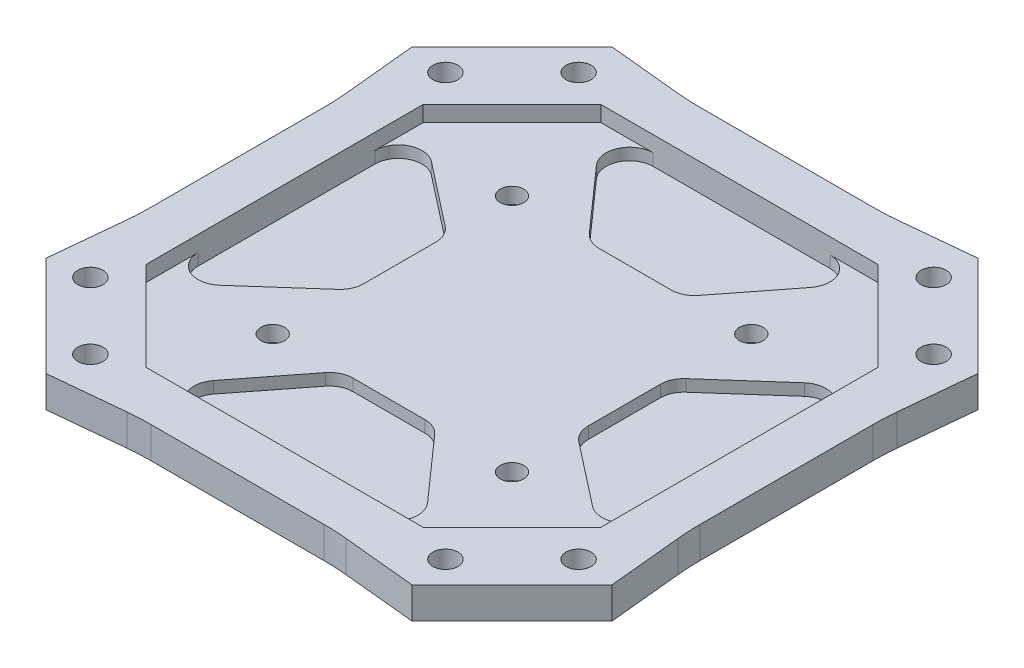
SolidWorks part; units mm, degrees
ref_plane "Front Plane" through (0, 0, 0) normal (0, 0, 1) x (1, 0, 0)
ref_plane "Top Plane" through (0, 0, 0) normal (0, 1, 0) x (1, 0, 0)
ref_plane "Right Plane" through (0, 0, 0) normal (1, 0, 0) x (0, 0, -1)
sketch "Sketch1" plane through (0, 0, 0) normal (0, 1, 0) x (1, 0, 0)
  line L0 (-35, 12.5) -> (-36.0623, 23.3344)
  line L1 (-35, 35) -> (35, 35) construction
  line L2 (-35, 35) -> (-35, -35) construction
  line L3 (-35, -35) -> (35, -35) construction
  line L4 (35, 35) -> (35, -35) construction
  line L5 (-35, 35) -> (35, -35) construction
  line L6 (-35, -35) -> (35, 35) construction
  line L7 (-23.3344, 36.0623) -> (-36.0623, 23.3344)
  line L8 (-23.3344, 36.0623) -> (-12.5, 35)
  line L9 (36.0623, 23.3344) -> (35, 12.5)
  line L10 (12.5, 35) -> (23.3344, 36.0623)
  line L11 (36.0623, 23.3344) -> (23.3344, 36.0623)
  line L12 (23.3344, -36.0623) -> (12.5, -35)
  line L13 (35, -12.5) -> (36.0623, -23.3344)
  line L14 (23.3344, -36.0623) -> (36.0623, -23.3344)
  line L15 (-36.0623, -23.3344) -> (-35, -12.5)
  line L16 (-12.5, -35) -> (-23.3344, -36.0623)
  line L17 (-36.0623, -23.3344) -> (-23.3344, -36.0623)
  line L18 (-35, 12.5) -> (-35, -12.5)
  line L19 (-12.5, 35) -> (12.5, 35)
  line L20 (35, 12.5) -> (35, -12.5)
  line L21 (12.5, -35) -> (-12.5, -35)
  line L22 (33.2339, 20.506) -> (20.506, 33.2339) construction
  line L23 (-20.506, 33.2339) -> (-33.2339, 20.506) construction
  line L24 (-33.2339, -20.506) -> (-20.506, -33.2339) construction
  line L25 (20.506, -33.2339) -> (33.2339, -20.506) construction
  circle A0 centre (31.1126, 22.6273) radius 1.6
  circle A1 centre (22.6273, 31.1126) radius 1.6
  circle A2 centre (31.1126, -22.6273) radius 1.6
  circle A3 centre (22.6273, -31.1126) radius 1.6
  circle A4 centre (-22.6273, -31.1126) radius 1.6
  circle A5 centre (-31.1126, -22.6273) radius 1.6
  circle A6 centre (-31.1126, 22.6273) radius 1.6
  circle A7 centre (-22.6273, 31.1126) radius 1.6
  point P0 (0, 0)
  point P25 (0, 0)
  point P51 (0, 0)
  dimension "D9" = 3.2
  dimension "D10" = 3.2
  dimension "D15" = 3.2
  dimension "D1" = 70
  dimension "D2" = 5.6
  dimension "D3" = 5.6
  dimension "D4" = 22.5
  dimension "D5" = 22.5
  dimension "D6" = 18
  dimension "D7" = 4
  dimension "D11" = 6
  dimension "D12" = 6
  dimension "D14" = 6
  dimension "D8" = 4
  dimension "D13" = 4
extrude "Boss-Extrude1" add sketch "Sketch1" along normal blind 4
sketch "Sketch3" plane through (0, 4, 0) normal (0, 1, 0) x (1, 0, 0)
  line L0 (35, -12.5) -> (35, 12.5) construction
  line L1 (-17.6688, 29) -> (17.6688, 29)
  line L2 (-29, 17.6688) -> (-29, -17.6688)
  line L3 (-17.6688, -29) -> (17.6688, -29)
  line L4 (29, 17.6688) -> (29, -17.6688)
  line L5 (-23.3344, 23.3344) -> (23.3344, -23.3344) construction
  line L6 (-23.3344, -23.3344) -> (23.3344, 23.3344) construction
  line L7 (12.5, 35) -> (-12.5, 35) construction
  line L8 (-35, 12.5) -> (-35, -12.5) construction
  line L9 (-12.5, -35) -> (12.5, -35) construction
  line L43 (-16.9704, 29.6984) -> (-29.6984, 16.9704)
  line L44 (-17.6688, 29) -> (-29, 17.6688)
  line L46 (-29.6984, -16.9704) -> (-16.9704, -29.6984)
  line L47 (-29, -17.6688) -> (-17.6688, -29)
  line L49 (16.9704, -29.6984) -> (29.6984, -16.9704)
  line L50 (17.6688, -29) -> (29, -17.6688)
  line L52 (29.6984, 16.9704) -> (16.9704, 29.6984)
  line L53 (29, 17.6688) -> (17.6688, 29)
  point P0 (0, 0)
  dimension "D1" = 6
  dimension "D2" = 6
  dimension "D7" = 6
  dimension "D8" = 6
  dimension "D3" = 9
  dimension "D4" = 9
  dimension "D5" = 9
  dimension "D6" = 9
extrude "Cut-Extrude1" cut sketch "Sketch3" against normal blind 2
sketch "Sketch4" plane through (0, 2, 0) normal (0, 1, 0) x (1, 0, 0)
  line L0 (0, 0) -> (-29, 0) construction
  line L1 (-29, 17.6688) -> (-29, -17.6688) construction
  line L2 (-29, -11.002) -> (-29, 11.5201)
  line L3 (-24.1537, 13.8846) -> (-16.1537, 7.638)
  line L4 (-15, 5.2734) -> (-15, -3.9129)
  line L5 (-16.0104, -6.1582) -> (-24.0104, -13.2473)
  line L6 (13.8846, 24.1537) -> (7.638, 16.1537)
  line L7 (-11.002, 29) -> (11.5201, 29)
  line L8 (-6.1582, 16.0104) -> (-13.2473, 24.0104)
  line L9 (5.2734, 15) -> (-3.9129, 15)
  line L10 (24.1537, -13.8846) -> (16.1537, -7.638)
  line L11 (29, 11.002) -> (29, -11.5201)
  line L12 (16.0104, 6.1582) -> (24.0104, 13.2473)
  line L13 (15, -5.2734) -> (15, 3.9129)
  line L14 (-13.8846, -24.1537) -> (-7.638, -16.1537)
  line L15 (11.002, -29) -> (-11.5201, -29)
  line L16 (6.1582, -16.0104) -> (13.2473, -24.0104)
  line L17 (-5.2734, -15) -> (3.9129, -15)
  arc A0 (-29, -11.002) -> (-24.0104, -13.2473) centre (-26, -11.002) ccw
  arc A1 (-15, -3.9129) -> (-16.0104, -6.1582) centre (-18, -3.9129) cw
  arc A2 (-16.1537, 7.638) -> (-15, 5.2734) centre (-18, 5.2734) cw
  arc A3 (-29, 11.5201) -> (-24.1537, 13.8846) centre (-26, 11.5201) cw
  arc A4 (11.5201, 29) -> (13.8846, 24.1537) centre (11.5201, 26) cw
  arc A5 (-11.002, 29) -> (-13.2473, 24.0104) centre (-11.002, 26) ccw
  arc A6 (-3.9129, 15) -> (-6.1582, 16.0104) centre (-3.9129, 18) cw
  arc A7 (7.638, 16.1537) -> (5.2734, 15) centre (5.2734, 18) cw
  arc A8 (29, -11.5201) -> (24.1537, -13.8846) centre (26, -11.5201) cw
  arc A9 (29, 11.002) -> (24.0104, 13.2473) centre (26, 11.002) ccw
  arc A10 (15, 3.9129) -> (16.0104, 6.1582) centre (18, 3.9129) cw
  arc A11 (16.1537, -7.638) -> (15, -5.2734) centre (18, -5.2734) cw
  arc A12 (-11.5201, -29) -> (-13.8846, -24.1537) centre (-11.5201, -26) cw
  arc A13 (11.002, -29) -> (13.2473, -24.0104) centre (11.002, -26) ccw
  arc A14 (3.9129, -15) -> (6.1582, -16.0104) centre (3.9129, -18) cw
  arc A15 (-7.638, -16.1537) -> (-5.2734, -15) centre (-5.2734, -18) cw
  point P13 (-29, -17.6688)
  point P16 (-15, -5.2629)
  point P19 (-15, 6.7371)
  point P22 (-29, 17.6688)
  point P62 (0, 0)
  dimension "D3" = 3
  dimension "D1" = 12
  dimension "D2" = 15
  dimension "D4" = 4
extrude "Cut-Extrude2" cut sketch "Sketch4" against normal blind 1.5
sketch "Sketch5" plane through (0, 2, 0) normal (0, 1, 0) x (1, 0, 0)
  line L1 (-15.25, 15.25) -> (15.25, 15.25) construction
  line L2 (-15.25, 15.25) -> (-15.25, -15.25) construction
  line L3 (-15.25, -15.25) -> (15.25, -15.25) construction
  line L4 (15.25, 15.25) -> (15.25, -15.25) construction
  line L5 (-15.25, 15.25) -> (15.25, -15.25) construction
  line L6 (-15.25, -15.25) -> (15.25, 15.25) construction
  circle A0 centre (15.25, 15.25) radius 1.5
  circle A1 centre (15.25, -15.25) radius 1.5
  circle A2 centre (-15.25, -15.25) radius 1.5
  circle A3 centre (-15.25, 15.25) radius 1.5
  point P0 (0, 0)
  point P16 (0, 0)
  dimension "D2" = 3
  dimension "D1" = 30.5
extrude "Cut-Extrude3" cut sketch "Sketch5" against normal through all
fillet "Fillet1" radius 30 8 edges at (-35, 2, 12.5) (-35, 2, -12.5) (12.5, 2, -35) (-12.5, 2, -35) (12.5, 2, 35) (-12.5, 2, 35) (35, 2, -12.5) (35, 2, 12.5)
